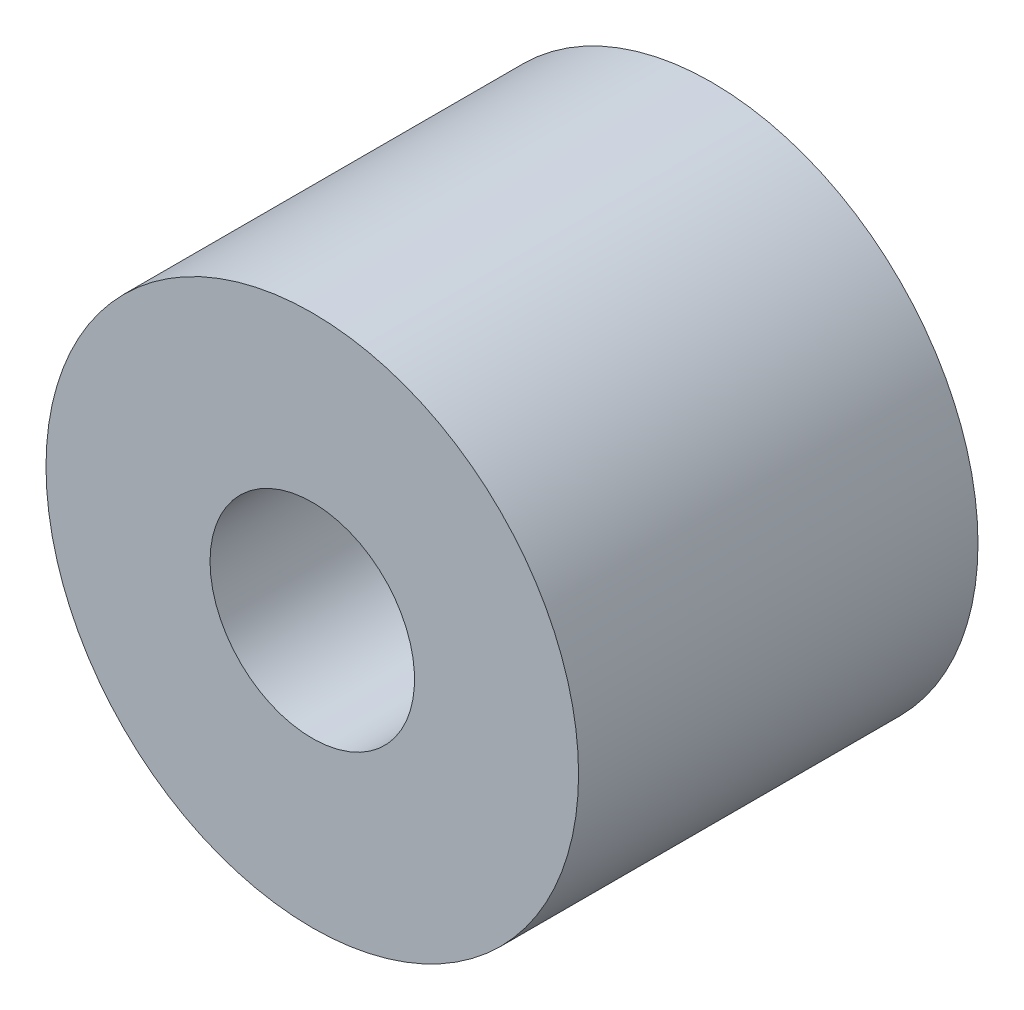
SolidWorks part; units mm, degrees
ref_plane "Front Plane" through (0, 0, 0) normal (0, 0, 1) x (1, 0, 0)
ref_plane "Top Plane" through (0, 0, 0) normal (0, 1, 0) x (1, 0, 0)
ref_plane "Right Plane" through (0, 0, 0) normal (1, 0, 0) x (0, 0, -1)
sketch "Sketch1" plane through (0, 0, 0) normal (0, 0, 1) x (1, 0, 0)
  circle A0 centre (0, 0) radius 6.35
  circle A1 centre (0, 0) radius 2.4384
  dimension "OD" = 12.7
  dimension "ID" = 4.8768
extrude "Extrude1" add sketch "Sketch1" along normal mid plane 9.525
sketch "Sketch2" plane through (0, 0, 0) normal (1, 0, 0) x (0, 0, -1)
  line L0 (-4.7625, -2.4384) -> (4.7625, -2.4384) construction
  line L3 (4.7625, 2.4384) -> (-4.7625, 2.4384) construction
  line L5 (-4.7625, -2.4384) -> (4.7625, -2.4384)
  line L6 (4.7625, 2.4384) -> (-4.7625, 2.4384)
sketch "Sketch4" plane through (0, 0, 4.7625) normal (0, 0, 1) x (1, 0, 0)
  line L0 (0, 0) -> (-1.7242, 1.7242)
  line L1 (0, -5.2388) -> (0, 5.2388) construction
  circle A0 centre (0, 0) radius 2.4384 construction
  dimension "D1" = 45
